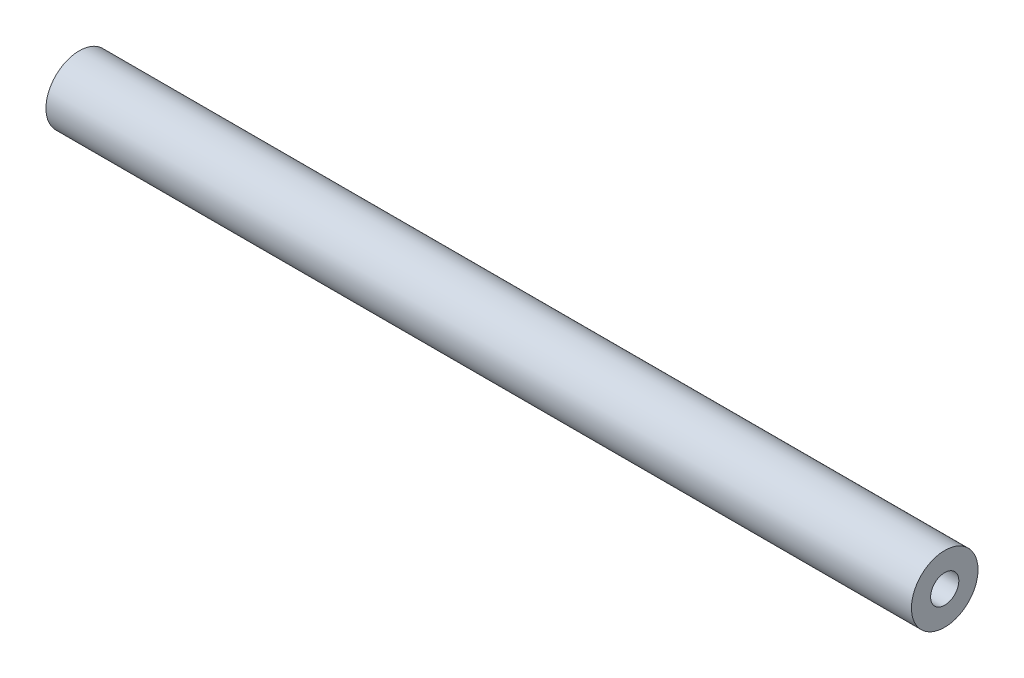
SolidWorks part; units mm, degrees
material "6061-T6 (SS)"
ref_plane "Front Plane" through (0, 0, 0) normal (0, 0, 1) x (1, 0, 0)
ref_plane "Top Plane" through (0, 0, 0) normal (0, 1, 0) x (1, 0, 0)
ref_plane "Right Plane" through (0, 0, 0) normal (1, 0, 0) x (0, 0, -1)
sketch "Sketch1" plane through (0, 0, 0) normal (1, 0, 0) x (0, 0, -1)
  circle A0 centre (0, 0) radius 4.7625
  dimension "D1" = 9.525
extrude "Boss-Extrude1" add sketch "Sketch1" along normal mid plane 123.825
hole_wizard "#10-32 Tapped Hole1" positions "3DSketch1" profile "Sketch2" tap size "#10-32" standard "ANSI Inch"
sketch3d "3DSketch1"
  line L0 (61.9125, 0, 0) -> (-61.9125, 0, 0) construction
  point P0 (61.9125, 0, 0)
  point P4 (-61.9125, 0, 0)
sketch "Sketch2" plane through (61.9125, 0, 0) normal (0, 1, 0) x (0, 0, -1)
  line L0 (0, 0) -> (0, 17.4693)
  line L1 (0, 17.4693) -> (2.0193, 16.256)
  line L2 (2.0193, 16.256) -> (2.0193, 0)
  line L5 (2.0193, 0) -> (0, 0)
  line L10 (0, 17.4693) -> (-2.0193, 16.256) construction
  line L11 (0, -6.35) -> (0, 107.95) construction
  dimension "Tap Drill Dia." = 4.0386
  dimension "Tap Drill Depth" = 16.256
  dimension "Drill Angle" = 118
cosmetic thread "Hole Thread1" parameters "D1"=13.97, "D2"=4.826
cosmetic thread "Hole Thread2" parameters "D1"=13.97, "D2"=4.826
